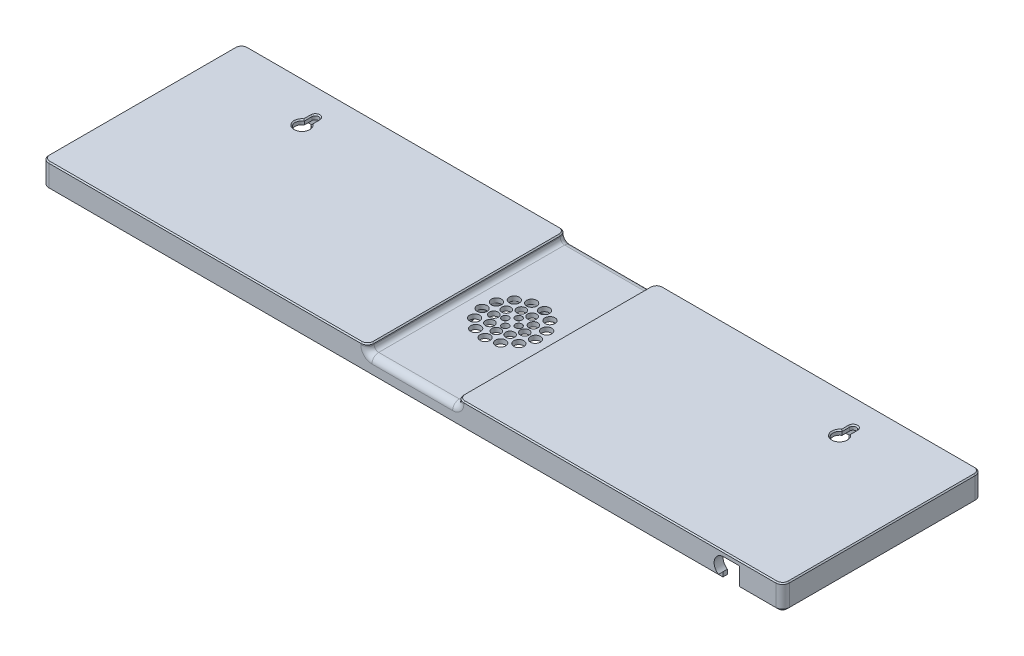
SolidWorks part; units mm, degrees
ref_plane "Front Plane" through (0, 0, 0) normal (0, 0, 1) x (1, 0, 0)
ref_plane "Top Plane" through (0, 0, 0) normal (0, 1, 0) x (1, 0, 0)
ref_plane "Right Plane" through (0, 0, 0) normal (1, 0, 0) x (0, 0, -1)
sketch "Sketch1" plane through (0, 0, 0) normal (0, 1, 0) x (1, 0, 0)
  line L1 (-163.25, 42.5) -> (163.25, 42.5)
  line L2 (-163.25, 42.5) -> (-163.25, -42.5)
  line L3 (-163.25, -42.5) -> (163.25, -42.5)
  line L4 (163.25, 42.5) -> (163.25, -42.5)
  line L5 (-163.25, 42.5) -> (163.25, -42.5) construction
  line L6 (-163.25, -42.5) -> (163.25, 42.5) construction
  line L7 (-161.25, 40.5) -> (161.25, 40.5)
  line L8 (-161.25, 40.5) -> (-161.25, -40.5)
  line L9 (-161.25, -40.5) -> (161.25, -40.5)
  line L10 (161.25, 40.5) -> (161.25, -40.5)
  line L11 (-161.25, 40.5) -> (161.25, -40.5) construction
  line L12 (-161.25, -40.5) -> (161.25, 40.5) construction
  point P0 (0, 0)
  point P6 (0, 0)
  dimension "D1" = 326.5
  dimension "D2" = 85
  dimension "D3" = 81
  dimension "D4" = 322.5
extrude "Boss-Extrude1" add sketch "Sketch1" along normal blind 10
sketch "Sketch2" plane through (0, 10, 0) normal (0, 1, 0) x (1, 0, 0)
  line L1 (-161.25, 40.5) -> (161.25, 40.5)
  line L2 (-161.25, 40.5) -> (-161.25, -40.5)
  line L3 (-161.25, -40.5) -> (161.25, -40.5)
  line L4 (161.25, 40.5) -> (161.25, -40.5)
  line L5 (-165.25, 44.5) -> (165.25, 44.5)
  line L6 (-165.25, 44.5) -> (-165.25, -44.5)
  line L7 (-165.25, -44.5) -> (165.25, -44.5)
  line L8 (165.25, 44.5) -> (165.25, -44.5)
  line L9 (-165.25, 44.5) -> (165.25, -44.5) construction
  line L10 (-165.25, -44.5) -> (165.25, 44.5) construction
  point P6 (0, 0)
  dimension "D1" = 4
  dimension "D2" = 4
extrude "Boss-Extrude2" add sketch "Sketch2" against normal blind 8
sketch "Sketch3" plane through (0, 10, 0) normal (0, 1, 0) x (1, 0, 0)
  line L1 (-165.25, 44.5) -> (165.25, 44.5)
  line L2 (-165.25, 44.5) -> (-165.25, -44.5)
  line L3 (-165.25, -44.5) -> (165.25, -44.5)
  line L4 (165.25, 44.5) -> (165.25, -44.5)
extrude "Boss-Extrude3" add sketch "Sketch3" along normal blind 2
fillet "Fillet1" radius 3 4 edges at (-161.25, 5, -40.5) (-161.25, 5, 40.5) (161.25, 5, 40.5) (161.25, 5, -40.5)
fillet "Fillet2" radius 2 4 edges at (-163.25, 1, -42.5) (-163.25, 1, 42.5) (163.25, 1, 42.5) (163.25, 1, -42.5)
fillet "Fillet3" radius 3 4 edges at (165.25, 7, -44.5) (165.25, 7, 44.5) (-165.25, 7, 44.5) (-165.25, 7, -44.5)
chamfer "Chamfer1" distance 0.5 angle 45 8 edges at (0, 12, 44.5) (164.3713, 12, 43.6213) (-164.3713, 12, 43.6213) (165.25, 12, 0) (-165.25, 12, 0) (164.3713, 12, -43.6213) (-164.3713, 12, -43.6213) (0, 12, -44.5)
sketch "Sketch4" plane through (0, 12, 0) normal (0, 1, 0) x (1, 0, 0)
  line L0 (0, 0) -> (0, 32.2227) construction
  line L1 (0, 32.2227) -> (120, 32.2227) construction
  line L2 (0, 32.2227) -> (-120, 32.2227) construction
  line L3 (-120, 32.2227) -> (-120, 26.2227) construction
  line L4 (120, 32.2227) -> (120, 26.2227) construction
  line L5 (-121.5, 32.2227) -> (-121.5, 28.8208)
  line L6 (-118.5, 32.2227) -> (-118.5, 28.8208)
  line L7 (118.5, 32.2227) -> (118.5, 28.8208)
  line L8 (121.5, 32.2227) -> (121.5, 28.8208)
  arc A0 (-121.5, 28.8208) -> (-118.5, 28.8208) centre (-120, 26.2227) ccw
  arc A1 (118.5, 28.8208) -> (121.5, 28.8208) centre (120, 26.2227) ccw
  arc A2 (-118.5, 32.2227) -> (-121.5, 32.2227) centre (-120, 32.2227) ccw
  arc A3 (121.5, 32.2227) -> (118.5, 32.2227) centre (120, 32.2227) ccw
  dimension "D3" = 6
  dimension "D4" = 6
  dimension "D7" = 3
  dimension "D8" = 3
  dimension "D1" = 120
  dimension "D2" = 120
  dimension "D5" = 6
  dimension "D6" = 6
extrude "Cut-Extrude1" cut sketch "Sketch4" against normal through all
chamfer "Chamfer2" distance 0.5 angle 45 8 edges at (118.5, 12, -30.5217) (120, 12, -33.7227) (121.5, 12, -30.5217) (120, 12, -23.2227) (-121.5, 12, -30.5217) (-120, 12, -33.7227) (-118.5, 12, -30.5217) (-120, 12, -23.2227)
sketch "Sketch7" plane through (0, 0, -44.5) normal (0, 0, -1) x (-1, 0, 0)
  line L0 (0, 0) -> (0, 9) construction
  line L1 (-161.25, 0) -> (161.25, 0) construction
  line L2 (0, 9) -> (-20, 9) construction
  line L3 (0, 9) -> (20, 9) construction
  line L4 (-162.25, 12) -> (162.25, 12) construction
  line L5 (-20, 9) -> (-20, 15.166)
  line L6 (-20, 15.166) -> (20, 15.166)
  line L7 (20, 15.166) -> (20, 9)
  line L8 (20, 9) -> (-20, 9)
  dimension "D1" = 20
  dimension "D2" = 20
  dimension "D3" = 3
extrude "Cut-Extrude3" cut sketch "Sketch7" against normal through all
sketch "Sketch8" plane through (0, 0, -44.5) normal (0, 0, -1) x (-1, 0, 0)
  line L0 (-20, 12) -> (-20, 9)
  line L1 (-20, 9) -> (20, 9)
  line L2 (20, 9) -> (20, 12)
  line L3 (20, 12) -> (22, 12)
  line L4 (20, 12) -> (162.25, 12) construction
  line L5 (22, 12) -> (22, 7)
  line L6 (22, 7) -> (-22, 7)
  line L7 (-22, 7) -> (-22, 12)
  line L8 (-162.25, 12) -> (-20, 12) construction
  line L13 (-20, 11.5) -> (-20, 12)
  line L14 (-20, 12) -> (-162.25, 12)
  line L15 (-162.25, 12) -> (-162.25, 11.5)
  line L16 (-162.25, 11.5) -> (-20, 11.5)
  line L18 (-20, 12) -> (-22, 12)
  dimension "D1" = 2
  dimension "D2" = 2
  dimension "D3" = 2
  dimension "D4" = 0
extrude "Boss-Extrude4" add sketch "Sketch8" against normal up to surface (89 mm away) up to face at (0, 8.5, 44.5)
fillet "Fillet4" radius 2 2 edges at (-20, 9, 0) (20, 9, 0)
chamfer "Chamfer3" distance 0.5 angle 45 2 edges at (21, 12, 44.5) (21, 12, -44.5)
fillet "Fillet5" radius 3 10 edges at (20, 11.25, 44.5) (19.4142, 9.5858, 44.5) (-20, 11.25, 44.5) (-19.4142, 9.5858, 44.5) (20, 11.25, -44.5) (19.4142, 9.5858, -44.5) (-20, 11.25, -44.5) (-19.4142, 9.5858, -44.5) (0, 9, -44.5) (0, 9, 44.5)
fillet "Fillet6" radius 2 2 edges at (-22, 10, 0) (22, 10, 0)
sketch "Sketch9" plane through (0, 7, 0) normal (0, -1, 0) x (1, 0, 0)
  circle A0 centre (0, 0) radius 14.25
  circle A1 centre (0, 0) radius 16.25
  dimension "D1" = 28.5
  dimension "D2" = 32.5
extrude "Boss-Extrude5" add sketch "Sketch9" along normal blind 3
sketch "Sketch10" plane through (0, 7, 0) normal (0, -1, 0) x (1, 0, 0)
  line L0 (0, 0) -> (0, 14.25) construction
  circle A0 centre (0, 0) radius 14.25 construction
  circle A1 centre (0, 3) radius 1.5
  circle A2 centre (0, 7) radius 2
  circle A3 centre (0, 12) radius 2.25
  circle A5 centre (4.4995, 5.3623) radius 2
  circle A8 centre (6.8937, 1.2155) radius 2
  circle A11 centre (6.0622, -3.5) radius 2
  circle A14 centre (2.3941, -6.5778) radius 2
  circle A17 centre (-2.3941, -6.5778) radius 2
  circle A20 centre (-6.0622, -3.5) radius 2
  circle A23 centre (-6.8937, 1.2155) radius 2
  circle A26 centre (-4.4995, 5.3623) radius 2
  circle A28 centre (-2.9544, 0.5209) radius 1.5 [skipped]
  circle A29 centre (-1.9284, 2.2981) radius 1.5 [skipped]
  circle A30 centre (-2.5981, -1.5) radius 1.5 [skipped]
  circle A31 centre (-1.0261, -2.8191) radius 1.5 [skipped]
  circle A32 centre (1.0261, -2.8191) radius 1.5 [skipped]
  circle A33 centre (2.9544, 0.5209) radius 1.5 [skipped]
  circle A34 centre (2.5981, -1.5) radius 1.5 [skipped]
  circle A35 centre (1.9284, 2.2981) radius 1.5 [skipped]
  circle A36 centre (3, 0) radius 1.5
  circle A37 centre (0, -3) radius 1.5
  circle A38 centre (-3, 0) radius 1.5
  circle A39 centre (-7.7135, 9.1925) radius 2.25 [skipped]
  circle A40 centre (-11.8177, 2.0838) radius 2.25 [skipped]
  circle A41 centre (-10.3923, -6) radius 2.25 [skipped]
  circle A42 centre (-4.1042, -11.2763) radius 2.25 [skipped]
  circle A43 centre (4.1042, -11.2763) radius 2.25 [skipped]
  circle A44 centre (10.3923, -6) radius 2.25 [skipped]
  circle A45 centre (11.8177, 2.0838) radius 2.25 [skipped]
  circle A46 centre (7.7135, 9.1925) radius 2.25 [skipped]
  circle A47 centre (5.5767, 10.6255) radius 2.25
  circle A48 centre (9.8758, 6.8168) radius 2.25
  circle A49 centre (11.9125, 1.4464) radius 2.25
  circle A50 centre (11.2202, -4.2553) radius 2.25
  circle A51 centre (7.9575, -8.9821) radius 2.25
  circle A52 centre (2.8718, -11.6513) radius 2.25
  circle A53 centre (-2.8718, -11.6513) radius 2.25
  circle A54 centre (-7.9575, -8.9821) radius 2.25
  circle A55 centre (-11.2202, -4.2553) radius 2.25
  circle A56 centre (-11.9125, 1.4464) radius 2.25
  circle A57 centre (-9.8758, 6.8168) radius 2.25
  circle A58 centre (-5.5767, 10.6255) radius 2.25
  dimension "D1" = 3
  dimension "D4" = 4
  dimension "D5" = 4.5
  dimension "D2" = 3
  dimension "D3" = 4
  dimension "D6" = 5
  dimension "D7" = 9
  dimension "D8" = 4
  dimension "D9" = 13
extrude "Cut-Extrude4" cut sketch "Sketch10" against normal through all
chamfer "Chamfer4" distance 0.5 angle 45 18 edges at (-22, 11.8358, 44.1642) (22, 11.8358, -44.1642) (20, 12, 0) (20.3566, 12, -42.9186) (20.3566, 12, 42.9186) (22, 11.8358, 44.1642) (21.6607, 11.8155, 44.1845) (22.4927, 11.5432, 44.4568) (-22.4927, 11.5432, 44.4568) (-21.6607, 11.8155, 44.1845) (-20, 12, 0) (-20.3566, 12, -42.9186) (-20.3566, 12, 42.9186) (22.4927, 11.5432, -44.4568) (21.6607, 11.8155, -44.1845) (-22, 11.8358, -44.1642) (-21.6607, 11.8155, -44.1845) (-22.4927, 11.5432, -44.4568)
sketch "Sketch12" plane through (0, 10, 0) normal (0, -1, 0) x (1, 0, 0)
  line L0 (-158.25, 40.5) -> (158.25, 40.5) construction
  line L1 (129.65, 20.5) -> (156.25, 20.5)
  line L2 (129.65, 20.5) -> (129.65, -14.5)
  line L3 (129.65, -14.5) -> (156.25, -14.5)
  line L4 (156.25, 20.5) -> (156.25, -14.5)
  line L5 (161.25, 37.5) -> (161.25, -37.5) construction
  line L7 (127.65, -16.5) -> (158.25, -16.5)
  line L8 (127.65, -16.5) -> (127.65, 22.5)
  line L9 (127.65, 22.5) -> (158.25, 22.5)
  line L10 (158.25, -16.5) -> (158.25, 22.5)
  line L11 (127.65, -16.5) -> (158.25, 22.5) construction
  line L12 (127.65, 22.5) -> (158.25, -16.5) construction
  point P8 (142.95, 3)
  dimension "D1" = 26.6
  dimension "D2" = 35
  dimension "D3" = 5
  dimension "20" = 20
  dimension "D4" = 2
  dimension "D5" = 2
  dimension "D6" = 2
  dimension "D7" = 2
extrude "Boss-Extrude6" add sketch "Sketch12" along normal blind 6
sketch "Sketch13" plane through (0, 10, 0) normal (0, -1, 0) x (1, 0, 0)
  line L0 (129.65, -14.5) -> (156.25, -14.5) construction
  line L1 (127.65, -12.5) -> (158.25, -12.5)
  line L2 (127.65, -12.5) -> (127.65, -16.5)
  line L3 (127.65, -16.5) -> (158.25, -16.5)
  line L4 (158.25, -12.5) -> (158.25, -16.5)
  line L5 (127.65, -12.5) -> (158.25, -16.5) construction
  line L6 (127.65, -16.5) -> (158.25, -12.5) construction
  point P0 (142.95, -14.5)
extrude "Boss-Extrude7" add sketch "Sketch13" along normal blind 2.7
sketch "Sketch14" plane through (0, 4, 0) normal (0, -1, 0) x (1, 0, 0)
  line L0 (156.25, -12.5) -> (156.25, 20.5) construction
  line L1 (156.25, 24.0241) -> (159.6238, 24.0241)
  line L2 (156.25, 24.0241) -> (156.25, 8.1247)
  line L3 (156.25, 8.1247) -> (159.6238, 8.1247)
  line L4 (159.6238, 24.0241) -> (159.6238, 8.1247)
  line L5 (135.6808, 24.5174) -> (150.9936, 24.5174)
  line L6 (135.6808, 24.5174) -> (135.6808, 18.4109)
  line L7 (135.6808, 18.4109) -> (150.9936, 18.4109)
  line L8 (150.9936, 24.5174) -> (150.9936, 18.4109)
  line L10 (125.8438, 11.915) -> (132.5475, 11.915)
  line L11 (125.8438, 11.915) -> (125.8438, -6.1679)
  line L12 (125.8438, -6.1679) -> (132.5475, -6.1679)
  line L13 (132.5475, 11.915) -> (132.5475, -6.1679)
  point P4 (125.8438, 11.915)
extrude "Cut-Extrude5" cut sketch "Sketch14" against normal up to surface (6 mm away) up to face at (142.95, 10, 4)
fillet "Fillet7" radius 2 5 edges at (150.9936, 7, 20.5) (135.6808, 7, 20.5) (129.65, 7, 11.915) (156.25, 7, 8.1247) (129.65, 7, -6.1679)
sketch "Sketch15" plane through (0, 0, -40.5) normal (0, 0, 1) x (1, 0, 0)
  line L0 (163.25, 2) -> (144.2097, 2) construction
  line L2 (142.7324, 8.8331) -> (145.6871, 8.8331)
  line L4 (142.7324, 4.4331) -> (145.6871, 4.4331)
  line L6 (139.6479, 8.8331) -> (148.7716, 4.4331) construction
  line L7 (139.6479, 4.4331) -> (148.7716, 8.8331) construction
  arc A0 (142.7324, 8.8331) -> (142.7324, 4.4331) centre (144.2097, 6.6331) ccw
  arc A1 (145.6871, 4.4331) -> (145.6871, 8.8331) centre (144.2097, 6.6331) ccw
  point P2 (144.2097, 6.6331)
  dimension "D1" = 5.3
  dimension "D2" = 4.4
extrude "Cut-Extrude6" cut sketch "Sketch15" against normal blind 12.7
sketch "Sketch16" plane through (0, 0, 40.5) normal (0, 0, -1) x (-1, 0, 0)
  line L0 (-134.7143, 5.6137) -> (-146.1143, 5.6137) construction
  line L1 (-146.1143, 9.9887) -> (-139.0893, 9.9887)
  line L3 (-146.1143, 1.2387) -> (-139.0893, 1.2387)
  line L5 (-147.8393, 9.9887) -> (-139.0893, 1.2387) construction
  line L6 (-147.8393, 1.2387) -> (-139.0893, 9.9887) construction
  line L7 (-146.1143, 5.6137) -> (-146.1143, 9.9887)
  line L8 (-146.1143, 5.6137) -> (-146.1143, 1.2387)
  line L9 (-147.8393, 9.9887) -> (-147.8393, 1.2387) construction
  line L10 (-147.8393, 1.2387) -> (-139.0893, 1.2387) construction
  arc A0 (-139.0893, 1.2387) -> (-139.0893, 9.9887) centre (-139.0893, 5.6137) ccw
  point P1 (-140.7734, 5.182)
  point P2 (-143.4643, 5.6137)
  point P9 (-143.3203, 5.5198)
  point P12 (-143.4643, 5.3949)
  point P13 (0, 0)
  dimension "D1" = 8.75
  dimension "D2" = 11.4
  dimension "D3" = 8.75
  dimension "D4" = 8.75
extrude "Cut-Extrude7" cut sketch "Sketch16" against normal blind 12.7
sketch "Sketch17" plane through (0, 0, 44.5) normal (0, 0, 1) x (1, 0, 0)
  line L0 (136.6232, 2) -> (146.1143, 4.5715)
  line L1 (146.1143, 2) -> (146.1143, 9.9887) construction
  line L2 (146.1143, 4.5715) -> (146.1143, -5.0335)
  line L3 (146.1143, -5.0335) -> (136.6232, -4.4034)
  line L4 (136.6232, -4.4034) -> (136.6232, 2)
extrude "Cut-Extrude8" cut sketch "Sketch17" against normal blind 12.7
sketch "Sketch18" plane through (0, 12, 0) normal (0, 1, 0) x (1, 0, 0)
  line L1 (-30.0055, 62.2614) -> (-176.0689, 62.2614)
  line L2 (-30.0055, 62.2614) -> (-30.0055, -69.4548)
  line L3 (-30.0055, -69.4548) -> (-176.0689, -69.4548)
  line L4 (-176.0689, 62.2614) -> (-176.0689, -69.4548)
  point P4 (-176.0689, 62.2614)
  point P5 (-30.0055, -69.4548)
sketch "Sketch19" plane through (0, 10, 0) normal (0, -1, 0) x (1, 0, 0)
  line L1 (37.7413, -4.0841) -> (58.7413, -4.0841)
  line L2 (37.7413, -4.0841) -> (37.7413, -25.3841)
  line L3 (37.7413, -25.3841) -> (58.7413, -25.3841)
  line L4 (58.7413, -4.0841) -> (58.7413, -25.3841)
  line L5 (37.7413, -4.0841) -> (58.7413, -25.3841) construction
  line L6 (37.7413, -25.3841) -> (58.7413, -4.0841) construction
  line L7 (35.7413, -2.0841) -> (60.7413, -2.0841)
  line L8 (35.7413, -2.0841) -> (35.7413, -27.3841)
  line L9 (35.7413, -27.3841) -> (60.7413, -27.3841)
  line L10 (60.7413, -2.0841) -> (60.7413, -27.3841)
  line L11 (35.7413, -2.0841) -> (60.7413, -27.3841) construction
  line L12 (35.7413, -27.3841) -> (60.7413, -2.0841) construction
  point P0 (48.2413, -14.7341)
  point P5 (48.2413, -14.7341)
  point P10 (49.8356, -2.1792)
  point P11 (48.2413, -14.7341)
  dimension "D1" = 21.3
  dimension "D2" = 21
  dimension "D3" = 2
  dimension "D4" = 2
extrude "Boss-Extrude8" add sketch "Sketch19" along normal blind 6
sketch "Sketch20" plane through (0, 4, 0) normal (0, -1, 0) x (1, 0, 0)
  line L0 (35.7413, -27.3841) -> (60.7413, -27.3841) construction
  line L1 (39.7413, -21.738) -> (56.7413, -21.738)
  line L2 (39.7413, -21.738) -> (39.7413, -33.0301)
  line L3 (39.7413, -33.0301) -> (56.7413, -33.0301)
  line L4 (56.7413, -21.738) -> (56.7413, -33.0301)
  line L5 (39.7413, -21.738) -> (56.7413, -33.0301) construction
  line L6 (39.7413, -33.0301) -> (56.7413, -21.738) construction
  line L7 (37.7413, -4.0841) -> (37.7413, -25.3841) construction
  point P0 (48.2413, -27.3841)
  dimension "D1" = 2
extrude "Cut-Extrude9" cut sketch "Sketch20" against normal up to surface (6 mm away) up to face at (-120, 10, -29.4972)
fillet "Fillet8" radius 2 2 edges at (39.7413, 7, -25.3841) (56.7413, 7, -25.3841)
fillet "Fillet9" radius 2 5 edges at (158.25, 7, -16.5) (127.65, 7, -16.5) (127.65, 7, 22.5) (35.7413, 7, -2.0841) (60.7413, 7, -2.0841)
fillet "Fillet10" radius 1 3 edges at (16.25, 4, 0) (14.25, 4, 0) (16.25, 7, 0)
